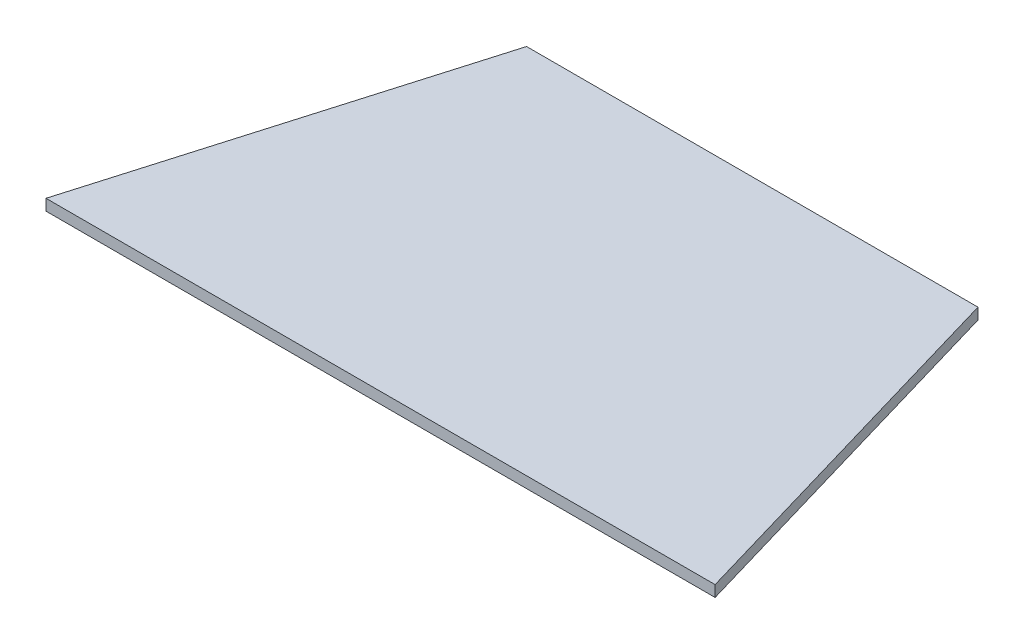
SolidWorks part; units mm, degrees
ref_plane "Front Plane" through (0, 0, 0) normal (0, 0, 1) x (1, 0, 0)
ref_plane "Top Plane" through (0, 0, 0) normal (0, 1, 0) x (1, 0, 0)
ref_plane "Right Plane" through (0, 0, 0) normal (1, 0, 0) x (0, 0, -1)
sketch "Sketch1" plane through (0, 0, 0) normal (0, 1, 0) x (1, 0, 0)
  line L0 (0, 0) -> (180, 0)
  line L3 (90, 0) -> (90, 100) construction
  line L5 (0, 0) -> (29.2799, 100)
  line L6 (180, 0) -> (150.7201, 100)
  line L7 (29.2799, 100) -> (150.7201, 100)
extrude "Boss-Extrude1" add sketch "Sketch1" along normal blind 3
